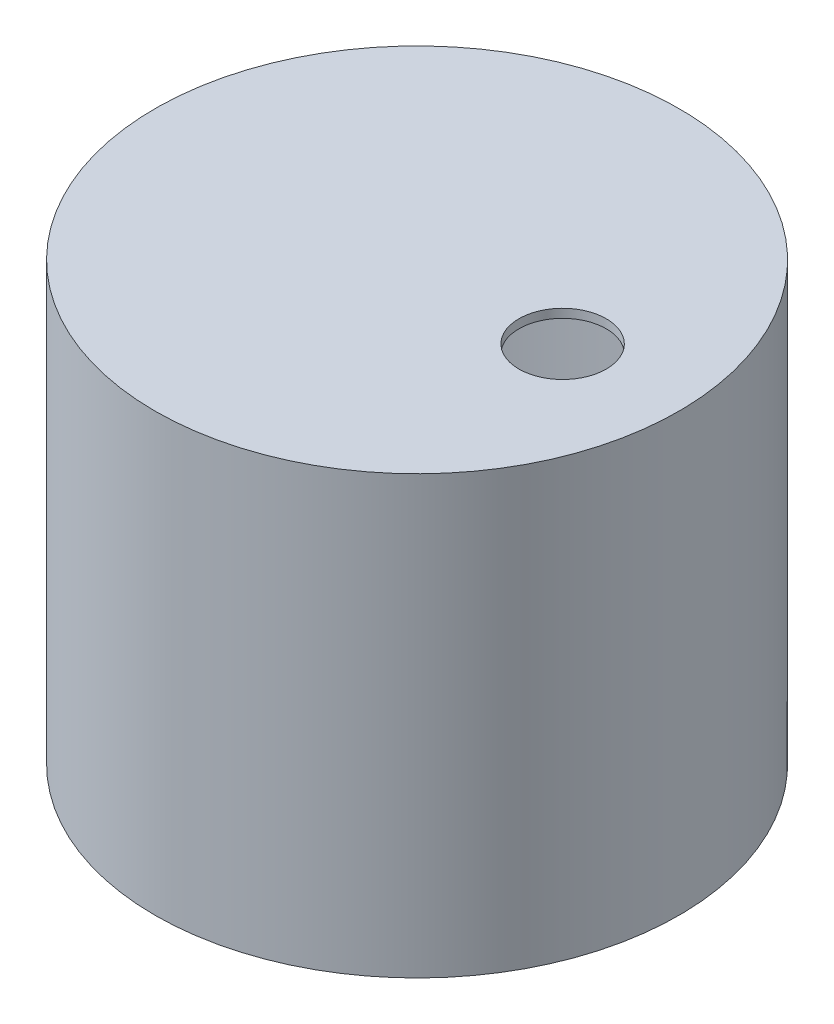
SolidWorks part; units mm, degrees
material "PE High Density"
ref_plane "Front Plane" through (0, 0, 0) normal (0, 0, 1) x (1, 0, 0)
ref_plane "Top Plane" through (0, 0, 0) normal (0, 1, 0) x (1, 0, 0)
ref_plane "Right Plane" through (0, 0, 0) normal (1, 0, 0) x (0, 0, -1)
sketch "Reservoir Wall Sketch" plane through (0, 0, 0) normal (0, 1, 0) x (1, 0, 0)
  circle A0 centre (0, 0) radius 180
  circle A1 centre (0, 0) radius 176
  dimension "D1" = 360
  dimension "D2" = 352
extrude "Reservoir Wall + Skirt" add sketch "Reservoir Wall Sketch" along normal blind 300
sketch "Reservoir Floor Sketch" plane through (0, 0, 0) normal (0, 1, 0) x (1, 0, 0)
  circle A0 centre (0, 0) radius 180
  circle A1 centre (0, 0) radius 10
  dimension "D1" = 360
  dimension "D2" = 20
extrude "Reservoir Floor" add sketch "Reservoir Floor Sketch" along normal blind 6 from offset 40
sketch "Sealed Lid Sketch" plane through (0, 0, 0) normal (0, 1, 0) x (1, 0, 0)
  circle A0 centre (0, 0) radius 180
  circle A1 centre (100, 0) radius 30
  dimension "D1" = 360
  dimension "D3" = 60
  dimension "D2" = 100
extrude "Sealed Lid" add sketch "Sealed Lid Sketch" along normal blind 6 from offset 294
